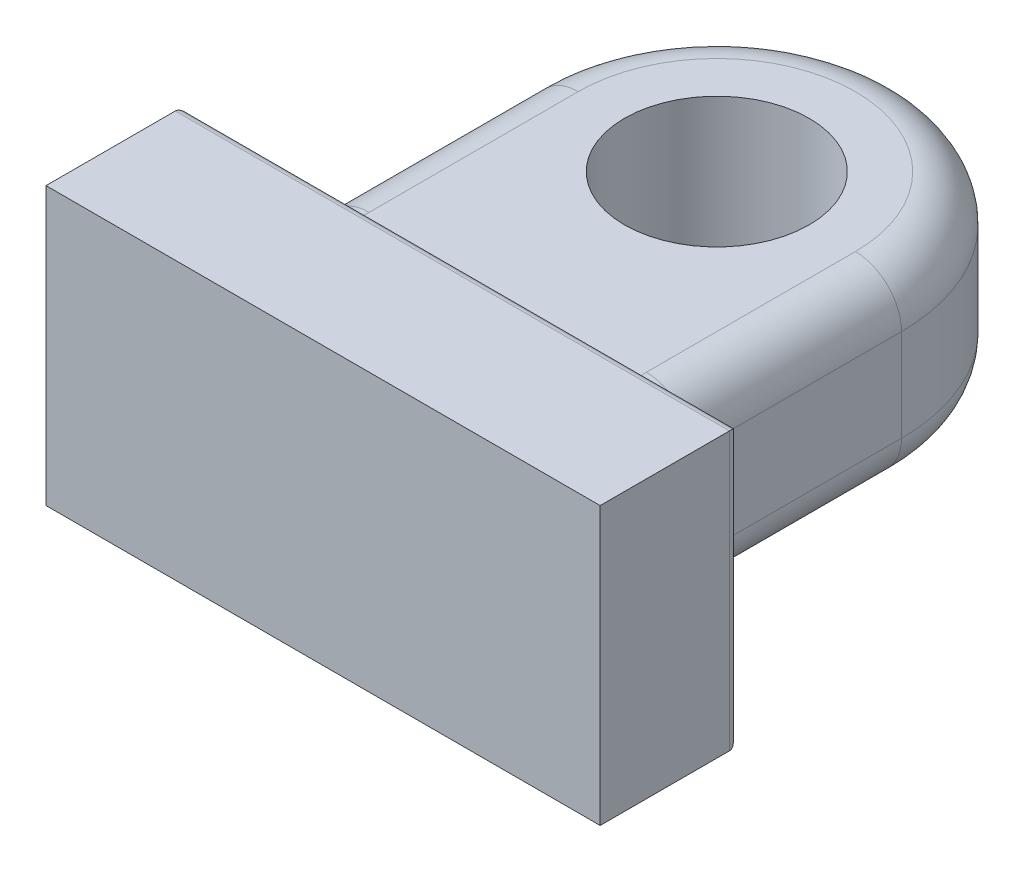
SolidWorks part; units mm, degrees
ref_plane "Front Plane" through (0, 0, 0) normal (0, 0, 1) x (1, 0, 0)
ref_plane "Top Plane" through (0, 0, 0) normal (0, 1, 0) x (1, 0, 0)
ref_plane "Right Plane" through (0, 0, 0) normal (1, 0, 0) x (0, 0, -1)
sketch "Sketch3" plane through (0, 0, 0) normal (0, 0, 1) x (1, 0, 0)
  line L1 (0, 0) -> (60, 0)
  line L2 (0, 0) -> (0, -30)
  line L3 (0, -30) -> (60, -30)
  line L4 (60, 0) -> (60, -30)
  dimension "D1" = 60
  dimension "D2" = 30
extrude "Boss-Extrude1" add sketch "Sketch3" along normal blind 15
ref_plane "Plane2" through (0, -15, 0) normal (0, 1, 0) x (1, 0, 0)
sketch "Sketch4" plane through (0, -15, 0) normal (0, 1, 0) x (1, 0, 0)
  line L0 (10, 27.6315) -> (10, 0)
  line L1 (60, 0) -> (0, 0) construction
  line L2 (10, 0) -> (50, 0)
  line L3 (50, 0) -> (50, 27.6315)
  line L4 (60, -15) -> (60, 0) construction
  circle A0 centre (30, 27.6315) radius 10
  arc A1 (50, 27.6315) -> (10, 27.6315) centre (30, 27.6315) ccw
  dimension "D1" = 20
  dimension "D2" = 20
  dimension "D3" = 27.6315
  dimension "D4" = 10
extrude "Boss-Extrude2" add sketch "Sketch4" along normal mid plane 20
fillet "Fillet1" radius 5 2 edges at (50, -15, 0) (10, -15, 0)
fillet "Fillet2" radius 5 10 edges at (51.4645, -25, -1.4645) (8.5355, -25, -1.4645) (10, -25, -16.3158) (30, -25, -47.6315) (51.4645, -5, -1.4645) (50, -5, -16.3158) (8.5355, -5, -1.4645) (10, -5, -16.3158) (50, -25, -16.3158) (30, -5, -47.6315)
fillet "Fillet3" radius 1 10 edges at (30, -30, 0) (60, -15, 0) (30, 0, 0) (0, -15, 0) (11.1603, -5.4468, 0) (30, -5, 0) (48.8397, -5.4468, 0) (48.8397, -24.5532, 0) (30, -25, 0) (11.1603, -24.5532, 0)
sketch "Sketch5" plane through (0, 0, 15) normal (0, 0, 1) x (1, 0, 0)
  line L0 (30, 0) -> (30, -30) construction
  line L1 (60, 0) -> (0, 0) construction
  line L2 (0, -30) -> (60, -30) construction
